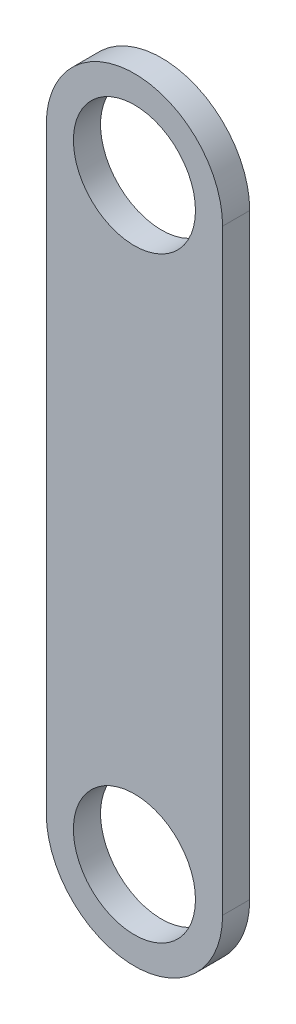
SolidWorks part; units mm, degrees
ref_plane "Front Plane" through (0, 0, 0) normal (0, 0, 1) x (1, 0, 0)
ref_plane "Top Plane" through (0, 0, 0) normal (0, 1, 0) x (1, 0, 0)
ref_plane "Right Plane" through (0, 0, 0) normal (1, 0, 0) x (0, 0, -1)
sketch "Sketch2" plane through (0, 0, 0) normal (0, 0, 1) x (1, 0, 0)
  line L0 (20.6375, 139.7) -> (20.6375, 0)
  line L1 (-20.6375, 139.7) -> (-20.6375, 0)
  circle A0 centre (0, 0) radius 14.2875
  circle A1 centre (0, 139.7) radius 14.2875
  circle A2 centre (0, 139.7) radius 20.6375
  circle A3 centre (0, 0) radius 20.6375
  point P11 (0, 86.7569)
  dimension "D1" = 28.575
  dimension "D2" = 6.35
  dimension "D3" = 139.7
extrude "Boss-Extrude1" add sketch "Sketch2" along normal mid plane 6.35 contours A3 L0 A2 L1 | A2 A1 | A3 A0 region at (0, 119.6462, 0) region at (0, 69.85, 0) region at (0, -20.0538, 0)
